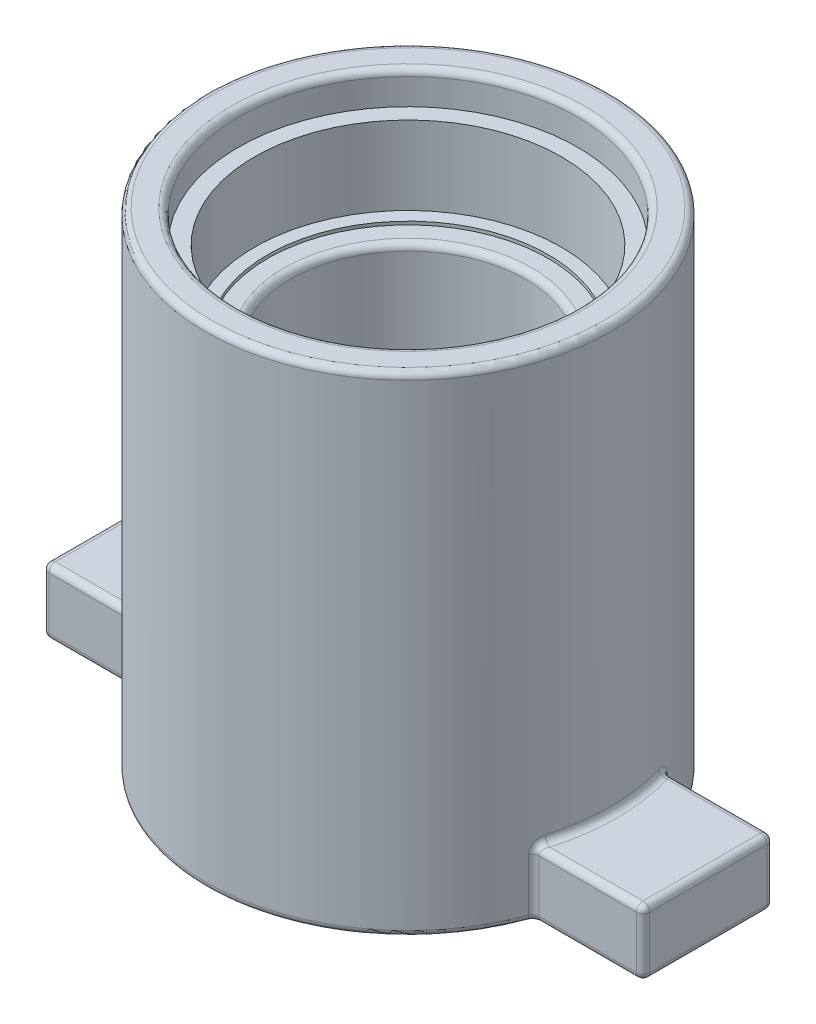
SolidWorks part; units mm, degrees
ref_plane "Ebene vorne" through (0, 0, 0) normal (0, 0, 1) x (1, 0, 0)
ref_plane "Ebene oben" through (0, 0, 0) normal (0, 1, 0) x (1, 0, 0)
ref_plane "Ebene rechts" through (0, 0, 0) normal (1, 0, 0) x (0, 0, -1)
sketch "Skizze1" plane through (0, 0, 0) normal (0, 0, 1) x (1, 0, 0)
  line L0 (18, -47.5) -> (18, -12.5)
  line L1 (18, -12.5) -> (21.5, -12.5)
  line L2 (21.5, -12.5) -> (21.5, -12)
  line L3 (21.5, -12) -> (23.5, -12)
  line L4 (23.5, -12) -> (23.5, 0)
  line L5 (23.5, 0) -> (26, 0)
  line L6 (31, 5) -> (31, -60)
  line L7 (31, -60) -> (23.5, -60)
  line L8 (23.5, -60) -> (23.5, -48)
  line L9 (23.5, -48) -> (21.5, -48)
  line L10 (21.5, -48) -> (21.5, -47.5)
  line L11 (21.5, -47.5) -> (18, -47.5)
  line L12 (26, 0) -> (26, 5)
  line L13 (26, 5) -> (31, 5)
  line L15 (0, 0) -> (0, -21.1983) construction
  line L17 (23.5, -60) -> (31, -60)
  line L18 (23.5, -60) -> (23.5, -70)
  line L19 (23.5, -70) -> (31, -70)
  line L20 (31, -60) -> (31, -70)
  line L21 (23.5, -60) -> (31, -70) construction
  line L22 (23.5, -70) -> (31, -60) construction
  point P20 (27.25, -65)
  dimension "D1" = 23.5
  dimension "D2" = 21.5
  dimension "D3" = 18
  dimension "D4" = 26
  dimension "D5" = 5
  dimension "D6" = 12
  dimension "D7" = 0.5
  dimension "D8" = 60
  dimension "D9" = 0.5
  dimension "D10" = 12
  dimension "D11" = 5
  dimension "D12" = 10
revolve "Rotation1" add sketch "Skizze1" angle 360 about L15 region at (25.4136, -28.7864, 0) region at (27.25, -65, 0)
ref_plane "Ebene1" through (31, 0, 0) normal (1, 0, 0) x (0, 0, -1)
sketch "Skizze2" plane through (31, 0, 0) normal (1, 0, 0) x (0, 0, -1)
  line L1 (-10, -70) -> (10, -70)
  line L2 (-10, -70) -> (-10, -60)
  line L3 (-10, -60) -> (10, -60)
  line L4 (10, -70) -> (10, -60)
  line L5 (-10, -70) -> (10, -60) construction
  line L6 (-10, -60) -> (10, -70) construction
  line L7 (-31, -70) -> (31, -70) construction
  point P0 (0, -65)
  point P7 (0, 0)
  dimension "D1" = 10
  dimension "D2" = 20
extrude "Aufsatz-Linear austragen1" add sketch "Skizze2" along normal blind 15 and the other way blind 6
mirror "Spiegeln1" about plane through (0, 0, 0) normal (1, 0, 0) of "Aufsatz-Linear austragen1"
fillet "Verrundung1" radius 1 29 edges at (29.3428, -65, 10) (29.3428, -65, -10) (-29.3428, -65, 10) (-29.3428, -65, -10) (37.6714, -60, 10) (31, -60, 0) (37.6714, -60, -10) (46, -65, 10) (46, -60, 0) (46, -65, -10) (-46, -65, 10) (-46, -65, -10) (-37.6714, -60, 10) (-46, -60, 0) (-37.6714, -60, -10) (-31, -60, 0) (0, -70, 23.5) (37.6714, -70, 10) (46, -70, 0) (37.6714, -70, -10) (0, -70, -31) (-37.6714, -70, -10) (-46, -70, 0) (-37.6714, -70, 10) (0, -70, 31) (0, 5, 26) (0, 5, 31) (0, -47.5, 18) (0, -12.5, 18)
